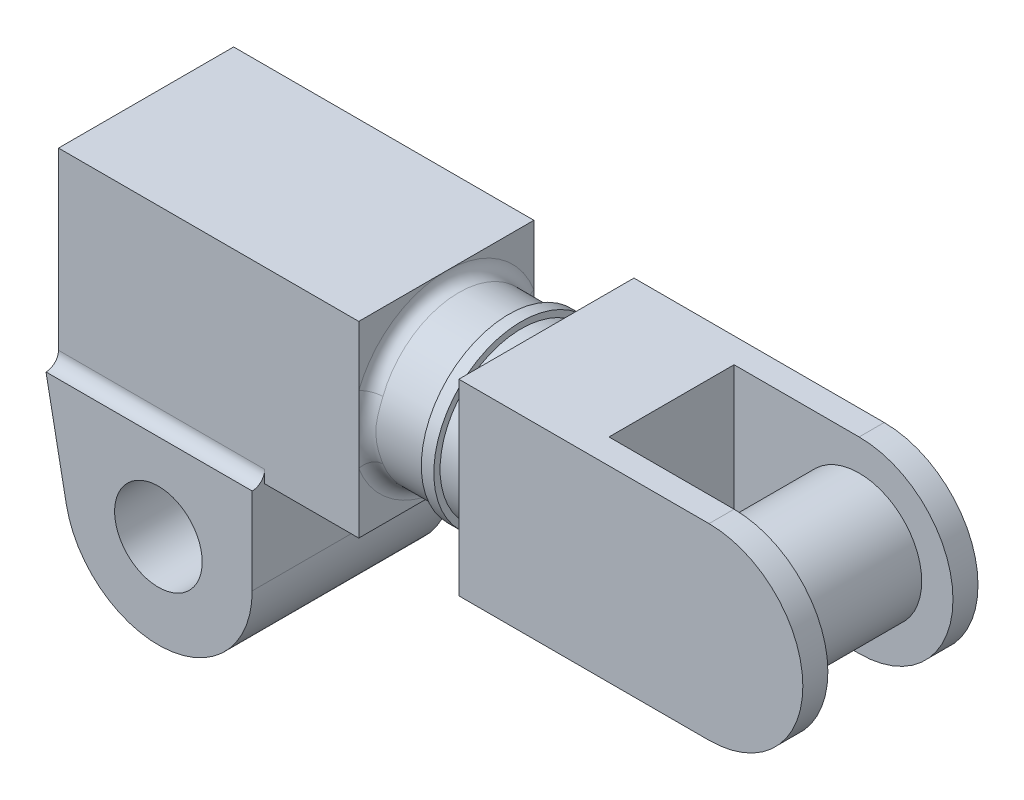
SolidWorks part; units mm, degrees
ref_plane "Ön Düzlem" through (0, 0, 0) normal (0, 0, 1) x (1, 0, 0)
ref_plane "Üst Düzlem" through (0, 0, 0) normal (0, 1, 0) x (1, 0, 0)
ref_plane "Sağ Düzlem" through (0, 0, 0) normal (1, 0, 0) x (0, 0, -1)
sketch "Çizim1" plane through (0, 0, 0) normal (1, 0, 0) x (0, 0, -1)
  line L1 (-70, 75) -> (70, 75)
  line L2 (-70, 75) -> (-70, -75)
  line L3 (-70, -75) -> (70, -75)
  line L4 (70, 75) -> (70, -75)
  line L5 (-70, 75) -> (70, -75) construction
  line L6 (-70, -75) -> (70, 75) construction
  point P0 (0, 0)
  dimension "D1" = 150
  dimension "D2" = 140
extrude "Yükseklik-Ekstrüzyon1" add sketch "Çizim1" along normal blind 240
sketch "Çizim2" plane through (240, 0, 0) normal (1, 0, 0) x (0, 0, -1)
  circle A0 centre (0, 0) radius 65
  dimension "D1" = 130
extrude "Yükseklik-Ekstrüzyon2" add sketch "Çizim2" along normal blind 50
sketch "Çizim3" plane through (290, 0, 0) normal (1, 0, 0) x (0, 0, -1)
  circle A0 centre (0, 0) radius 70
  dimension "D1" = 140
extrude "Yükseklik-Ekstrüzyon3" add sketch "Çizim3" along normal blind 10
sketch "Çizim4" plane through (0, 0, 0) normal (0, 0, 1) x (1, 0, 0)
  line L0 (0, -75) -> (16.2188, -158.4383)
  line L1 (0, 75) -> (0, -75) construction
  line L2 (164.8408, -144.1276) -> (164.8408, -75)
  line L3 (240, -75) -> (0, -75) construction
  line L4 (0, -75) -> (164.8408, -75)
  arc A0 (16.2188, -158.4383) -> (164.8408, -144.1276) centre (89.8408, -144.1276) ccw
  circle A1 centre (89.8408, -144.1276) radius 35
  dimension "D1" = 150
  dimension "D2" = 70
  dimension "D3" = 191
  dimension "D4" = 85
extrude "Yükseklik-Ekstrüzyon4" add sketch "Çizim4" along normal mid plane 160
fillet "Radyus1" radius 10 3 edges at (240, 0, -65) (82.4204, -75, -70) (82.4204, -75, 70)
sketch "Çizim5" plane through (300, 0, 0) normal (1, 0, 0) x (0, 0, -1)
  circle A0 centre (0, 0) radius 65
  dimension "D1" = 130
extrude "Yükseklik-Ekstrüzyon5" add sketch "Çizim5" along normal blind 20
sketch "Çizim6" plane through (0, 0, 0) normal (0, 0, 1) x (1, 0, 0)
  line L0 (520, 75) -> (320, 75)
  line L1 (320, 75) -> (320, -75)
  line L2 (320, -75) -> (520, -75)
  line L3 (320, -65) -> (320, 65) construction
  arc A0 (520, -75) -> (520, 75) centre (520, 0) ccw
  dimension "D1" = 150
  dimension "D2" = 200
extrude "Yükseklik-Ekstrüzyon6" add sketch "Çizim6" along normal mid plane 140
sketch "Çizim7" plane through (0, 0, 0) normal (0, 0, 1) x (1, 0, 0)
  line L0 (520, 75) -> (420, 75)
  line L1 (520, 75) -> (320, 75) construction
  line L2 (420, 75) -> (420, -75)
  line L3 (320, -75) -> (520, -75) construction
  line L4 (420, -75) -> (520, -75)
  arc A0 (520, -75) -> (520, 75) centre (520, 0) ccw construction
  arc A1 (520, -75) -> (520, 75) centre (520, 0) ccw
extrude "Kes-Ekstrüzyon1" cut sketch "Çizim7" against normal mid plane 100
sketch "Çizim8" plane through (0, 0, -50) normal (0, 0, 1) x (1, 0, 0)
  circle A0 centre (520, 0) radius 50
  dimension "D1" = 100
extrude "Yükseklik-Ekstrüzyon7" add sketch "Çizim8" along normal blind 100
